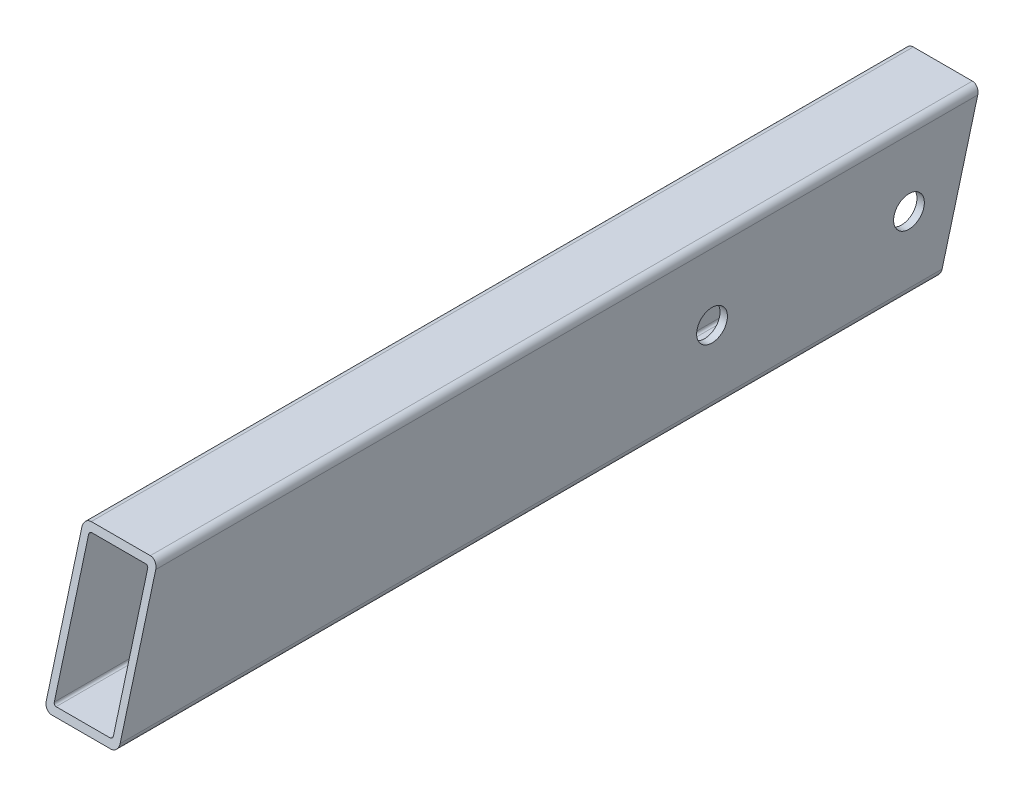
SolidWorks part; units mm, degrees
material "1.0114 (S235J0)"
ref_plane "Płaszczyzna przednia" through (0, 0, 0) normal (0, 0, 1) x (1, 0, 0)
ref_plane "Płaszczyzna górna" through (0, 0, 0) normal (0, 1, 0) x (1, 0, 0)
ref_plane "Płaszczyzna prawa" through (0, 0, 0) normal (1, 0, 0) x (0, 0, -1)
sketch "Szkic1" plane through (0, 0, 0) normal (0, 0, 1) x (1, 0, 0)
  line L0 (-7.1969, 27) -> (14.8031, 27)
  line L1 (-8.1969, -30) -> (15.8031, -30)
  line L2 (-11.1969, -27) -> (-11.1969, 27)
  line L3 (-8.1969, 30) -> (15.8031, 30)
  line L4 (18.8031, -27) -> (18.8031, 27)
  line L5 (15.8031, -26) -> (15.8031, 26)
  line L6 (-7.1969, -27) -> (14.8031, -27)
  line L7 (-8.1969, -26) -> (-8.1969, 26)
  line L8 (-11.1969, 30) -> (18.8031, 30) construction
  line L9 (18.8031, -30) -> (18.8031, 30) construction
  line L10 (-11.1969, -30) -> (18.8031, -30) construction
  line L11 (-11.1969, -30) -> (-11.1969, 30) construction
  line L12 (-8.1969, 27) -> (15.8031, 27) construction
  line L13 (15.8031, -27) -> (15.8031, 27) construction
  line L14 (-8.1969, -27) -> (15.8031, -27) construction
  line L15 (-8.1969, -27) -> (-8.1969, 27) construction
  line L16 (55, 0) -> (-55, 0) construction
  arc A0 (15.8031, 30) -> (18.8031, 27) centre (15.8031, 27) cw
  arc A1 (18.8031, -27) -> (15.8031, -30) centre (15.8031, -27) cw
  arc A2 (-8.1969, -30) -> (-11.1969, -27) centre (-8.1969, -27) cw
  arc A3 (-11.1969, 27) -> (-8.1969, 30) centre (-8.1969, 27) cw
  arc A4 (14.8031, 27) -> (15.8031, 26) centre (14.8031, 26) cw
  arc A5 (15.8031, -26) -> (14.8031, -27) centre (14.8031, -26) cw
  arc A6 (-7.1969, -27) -> (-8.1969, -26) centre (-7.1969, -26) cw
  arc A7 (-8.1969, 26) -> (-7.1969, 27) centre (-7.1969, 26) cw
  point P4 (-11.1969, 0)
  point P12 (15, 0)
  dimension "D4" = 3
  dimension "D1" = 1
  dimension "D2" = 30
  dimension "D5" = 60
  dimension "D3" = 3
extrude "Dodanie-wyciągnięcie1" add sketch "Szkic1" against normal blind 350
sketch "Szkic2" plane through (0, 0, 0) normal (1, 0, 0) x (0, 0, -1)
  line L2 (0, -30) -> (16.077, 30)
  line L4 (350, 30) -> (0, 30) construction
  line L5 (16.077, 30) -> (0, 30)
  line L6 (0, 30) -> (0, -30)
  line L7 (350, 30) -> (333.923, -30)
  line L8 (350, -30) -> (0, -30) construction
  line L9 (333.923, -30) -> (350, -30)
  line L10 (350, -30) -> (350, 30)
  dimension "D1" = 15
  dimension "D2" = 15
extrude "Wytnij-wyciągnięcie1" cut sketch "Szkic2" against normal blind 50 and the other way blind 52
sketch "Szkic3" plane through (0, 0, 0) normal (1, 0, 0) x (0, 0, -1)
  line L2 (334.7269, -27) -> (349.1962, 27) construction
  circle A0 centre (241.256, 0) radius 6.25
  circle A1 centre (321.256, 0) radius 6.25
  point P4 (0, 0)
  point P5 (0, 0)
  dimension "D2" = 12.5
  dimension "D1" = 80
  dimension "D3" = 20
extrude "Wytnij-wyciągnięcie2" cut sketch "Szkic3" against normal blind 26 and the other way blind 31
